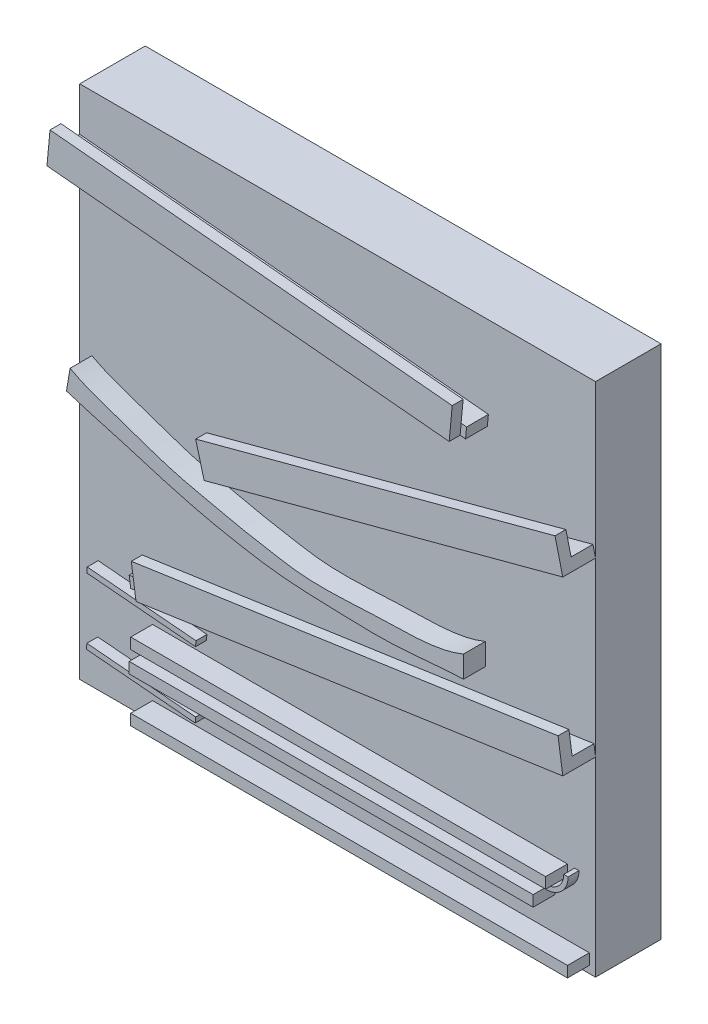
SolidWorks part; units mm, degrees
ref_plane "Front Plane" through (0, 0, 0) normal (0, 0, 1) x (1, 0, 0)
ref_plane "Top Plane" through (0, 0, 0) normal (0, 1, 0) x (1, 0, 0)
ref_plane "Right Plane" through (0, 0, 0) normal (1, 0, 0) x (0, 0, -1)
sketch "Sketch1" plane through (0, 0, 0) normal (0, 0, 1) x (1, 0, 0)
  line L0 (-525.2401, 242.9845) -> (-525.2401, 255.74)
  line L1 (-525.2401, 306.54) -> (74.7599, 306.54)
  line L2 (-525.2401, 306.54) -> (-525.2401, -293.46)
  line L3 (-525.2401, -293.46) -> (74.7599, -293.46)
  line L4 (74.7599, 306.54) -> (74.7599, -293.46)
  line L5 (-525.2401, 242.9845) -> (-57.3861, 199.1819)
  line L6 (-57.3861, 199.1819) -> (-53.8345, 237.116)
  line L7 (-525.2401, 242.9845) -> (-51.0637, 198.59)
  line L8 (-51.0637, 198.59) -> (-49.8799, 211.2347)
  line L9 (-49.8799, 211.2347) -> (-525.2401, 255.74)
  line L10 (-53.8345, 237.116) -> (-521.6885, 280.9186)
  line L11 (-521.6885, 280.9186) -> (-525.2401, 242.9845)
  line L12 (71.7445, 141.0797) -> (-345.7148, 29.6768)
  line L13 (-342.4403, 17.4062) -> (74.7599, 128.74)
  line L14 (74.7599, -71.6282) -> (72.9267, -59.0612)
  line L15 (74.7599, -71.6282) -> (69.2602, -33.9272)
  line L16 (-352.2639, 54.218) -> (-342.4403, 17.4062)
  line L17 (-352.2639, 54.218) -> (65.7136, 165.7592)
  line L18 (65.7136, 165.7592) -> (74.7599, 128.74)
  line L19 (-515.2325, 14.7313) -> (-511.0494, 39.7845)
  line L20 (-53.4611, -44.7009) -> (-53.4611, -19.3009)
  line L21 (74.7599, -71.6282) -> (-440.4866, -146.7913)
  line L22 (-440.4866, -146.7913) -> (-442.3198, -134.2243)
  line L23 (-442.3198, -134.2243) -> (72.9267, -59.0612)
  line L24 (74.7599, -71.6282) -> (-421.6361, -144.0415)
  line L25 (-421.6361, -144.0415) -> (-427.1359, -106.3405)
  line L26 (-427.1359, -106.3405) -> (69.2602, -33.9272)
  line L28 (-503.7945, -163.0687) -> (-377.2778, -174.1375)
  line L29 (-377.2778, -174.1375) -> (-377.8312, -180.4633)
  line L30 (-377.8312, -180.4633) -> (-504.3479, -169.3945)
  line L31 (-504.3479, -169.3945) -> (-503.7945, -163.0687)
  line L32 (-440.4866, -195.7033) -> (42.1134, -195.7033)
  line L33 (42.1134, -195.7033) -> (42.1134, -208.4033)
  line L34 (42.1134, -208.4033) -> (-440.4866, -208.4033)
  line L35 (-440.4866, -208.4033) -> (-440.4866, -195.7033)
  line L36 (50.4411, -195.7033) -> (55.5211, -195.7033)
  line L37 (30.1211, -216.0519) -> (30.1211, -221.1033)
  line L38 (27.5811, -221.1319) -> (-442.3189, -221.1319)
  line L39 (27.5811, -221.1319) -> (27.5811, -233.8319)
  line L40 (27.5811, -233.8319) -> (-442.3189, -233.8319)
  line L41 (-442.3189, -221.1319) -> (-442.3189, -233.8319)
  line L42 (-504.752, -246.4601) -> (-378.2353, -257.5289)
  line L43 (-378.2353, -257.5289) -> (-377.6818, -251.203)
  line L44 (-377.6818, -251.203) -> (-504.1986, -240.1343)
  line L45 (-504.1986, -240.1343) -> (-504.752, -246.4601)
  line L46 (-440.4866, -272.4603) -> (-440.4866, -285.1603)
  line L47 (-440.4866, -285.1603) -> (67.5134, -285.1603)
  line L48 (67.5134, -285.1603) -> (67.5134, -272.4603)
  line L49 (67.5134, -272.4603) -> (-440.4866, -272.4603)
  line L50 (74.7599, 141.8844) -> (74.7599, 128.74)
  line L51 (71.7445, 141.0797) -> (74.7599, 128.74)
  arc A0 (30.1211, -221.1033) -> (55.5211, -195.7033) centre (30.1211, -195.7033) ccw
  arc A1 (30.1211, -216.0519) -> (50.4698, -195.7033) centre (30.1211, -195.7033) ccw
  spline S0 degree 3 poles (-511.0494, 39.7845) (-491.9134, 29.2102) (-458.7786, 19.5317) (-416.626, 3.9591) (-383.9036, -6.2494) (-350.3154, -13.2529) (-315.5021, -21.5704) (-279.5185, -27.8081) (-243.8313, -34.152) (-199.4565, -34.7521) (-135.7138, -30.0004) (-83.078, -31.6613) (-53.4611, -19.3009) knots 0 0 0 0 0.138195 0.220154 0.287066 0.356885 0.439197 0.515633 0.590195 0.670344 0.79798 1 1 1 1
  spline S1 degree 3 poles (-515.2325, 14.7313) (-492.2874, 7.3612) (-460.6837, -0.7812) (-419.9744, -13.5025) (-388.8319, -22.4198) (-355.4555, -31.2767) (-317.591, -38.7813) (-279.774, -45.523) (-241.5923, -48.5929) (-194.7283, -49.9033) (-132.9072, -52.6237) (-81.9113, -45.613) (-53.4611, -44.7009) knots 0 0 0 0 0.153828 0.208265 0.272297 0.360673 0.42862 0.518727 0.605765 0.672841 0.818182 1 1 1 1
  point P0 (0, 0)
  point P26 (-511.0494, 39.7845)
  point P62 (27.5811, -221.1319)
  dimension "D11" = 203.2
  dimension "D14" = 25.4
  dimension "D23" = 469.9
  dimension "D24" = 469.9
  dimension "D28" = 15.24
  dimension "D29" = 5.08
  dimension "D30" = 25.4
  dimension "D31" = 20.3486
  dimension "D1" = 600
  dimension "D2" = 600
  dimension "D3" = 12.7
  dimension "D4" = 476.25
  dimension "D5" = 50.8
  dimension "D6" = 107.95
  dimension "D7" = 469.9
  dimension "D8" = 38.1
  dimension "D9" = 12.7
  dimension "D10" = 431.8
  dimension "D12" = 38.1
  dimension "D13" = 177.8
  dimension "D16" = 12.7
  dimension "D17" = 520.7
  dimension "D18" = 501.65
  dimension "D19" = 38.1
  dimension "D20" = 6.35
  dimension "D21" = 127
  dimension "D22" = 5
  dimension "D25" = 177.8
  dimension "D26" = 12.7
  dimension "D27" = 482.6
  dimension "D32" = 5.08
  dimension "D33" = 469.9
  dimension "D34" = 2.54
  dimension "D35" = 12.7
  dimension "D36" = 6.35
  dimension "D37" = 5
  dimension "D38" = 127
  dimension "D39" = 12.7
  dimension "D40" = 508
extrude "Boss-Extrude1" add sketch "Sketch1" against normal blind 76.2 contours L4 L3 L2 L1
extrude "Boss-Extrude2" add sketch "Sketch1<22>" along normal blind 25.4 contours L7 L8 L9 L0
sketch "Sketch1<22>" plane through (0, 0, 0) normal (0, 0, 1) x (1, 0, 0) same geometry as "Sketch1"
extrude "Boss-Extrude3" add sketch "Sketch1<23>" along normal blind 12.7 from offset 25.4 contours L5 L6 L10 L11
sketch "Sketch1<23>" plane through (0, 0, 0) normal (0, 0, 1) x (1, 0, 0) same geometry as "Sketch1"
extrude "Boss-Extrude4" add sketch "Sketch1<36>" along normal blind 25.4 contours L18 L12 region at (-135.4128, 79.2263, 0)
sketch "Sketch1<36>" plane through (0, 0, 0) normal (0, 0, 1) x (1, 0, 0) same geometry as "Sketch1"
extrude "Boss-Extrude5" add sketch "Sketch1<38>" along normal blind 12.7 from offset 25.4 contours L13 L16 L17 L18
sketch "Sketch1<38>" plane through (0, 0, 0) normal (0, 0, 1) x (1, 0, 0) same geometry as "Sketch1"
extrude "Boss-Extrude6" add sketch "Sketch1<39>" along normal blind 25.4 contours S1 L20 S0 L19
sketch "Sketch1<39>" plane through (0, 0, 0) normal (0, 0, 1) x (1, 0, 0) same geometry as "Sketch1"
extrude "Boss-Extrude7" add sketch "Sketch1<42>" along normal blind 25.4 contours L35 L34 L33 L32 | L38 L41 L40 L39 | L48 L49 L46 L47 region at (-199.1866, -202.0533, 0) region at (-207.3689, -227.4819, 0) region at (-186.4866, -278.8103, 0)
sketch "Sketch1<42>" plane through (0, 0, 0) normal (0, 0, 1) x (1, 0, 0) same geometry as "Sketch1"
extrude "Boss-Extrude8" add sketch "Sketch1<43>" along normal blind 12.7 contours L31 L30 L29 L28 | L44 L45 L42 L43 | A1 L37 A0 L36 region at (-440.8128, -171.766, 0) region at (44.7426, -210.3247, 0) region at (-441.2169, -248.8316, 0)
sketch "Sketch1<43>" plane through (0, 0, 0) normal (0, 0, 1) x (1, 0, 0) same geometry as "Sketch1"
extrude "Boss-Extrude9" add sketch "Sketch1<46>" along normal blind 12.7 from offset 25.4 separate body contours L24 L25 L26 L15
sketch "Sketch1<46>" plane through (0, 0, 0) normal (0, 0, 1) x (1, 0, 0) same geometry as "Sketch1"
extrude "Boss-Extrude10" add sketch "Sketch1<47>" along normal blind 25.4 contours L21 L25 L23 L22 | L25 L21 L14 L23 region at (-174.3547, -101.5513, 0) region at (-431.978, -139.1329, 0)
sketch "Sketch1<47>" plane through (0, 0, 0) normal (0, 0, 1) x (1, 0, 0) same geometry as "Sketch1"
